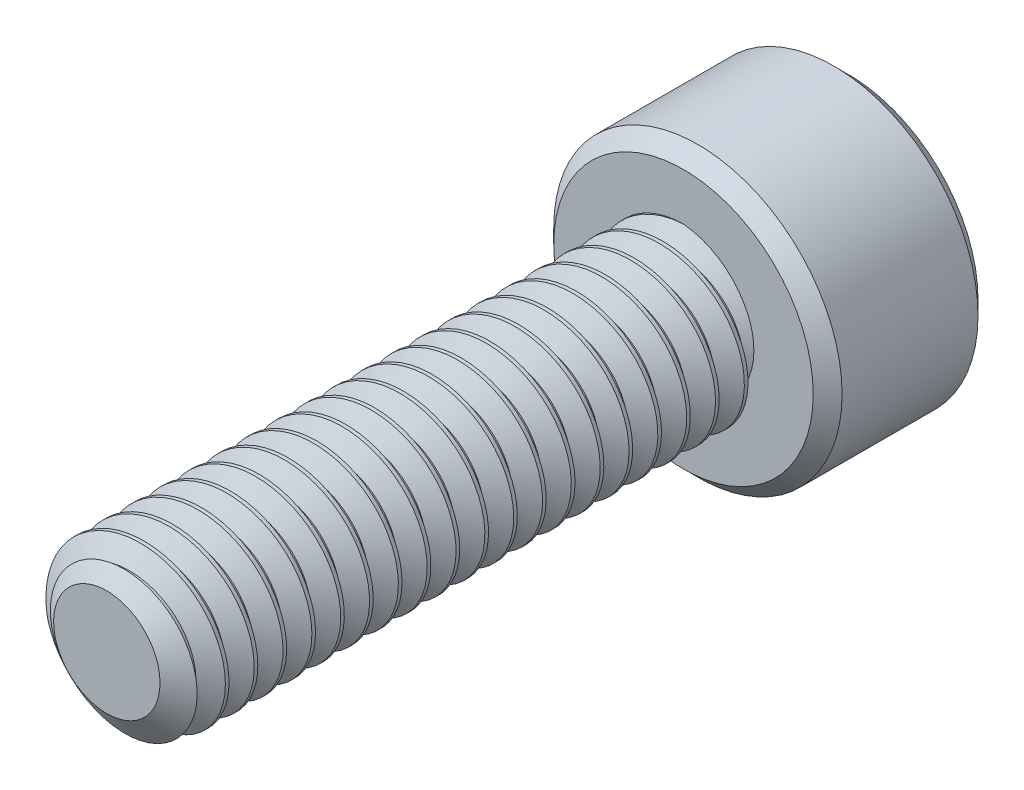
SolidWorks part; units mm, degrees
note: '?' marks a value the reader was unsure of.
other "DetailItem1"
material "Stainless Steel (ferritic)"
ref_plane "Front Plane" through (0, 0, 0) normal (0, 0, 1) x (1, 0, 0)
ref_plane "Top Plane" through (0, 0, 0) normal (0, 1, 0) x (1, 0, 0)
ref_plane "Right Plane" through (0, 0, 0) normal (1, 0, 0) x (0, 0, -1)
sketch "Sketch1" plane through (0, 0, 0) normal (0, 0, 1) x (1, 0, 0)
  circle A0 centre (0, 0) radius 2
  dimension "OD" = 4
extrude "Extrude1" add sketch "Sketch1" against normal blind 14
sketch "Sketch2" plane through (0, 0, 0) normal (0, 0, 1) x (1, 0, 0)
  circle A0 centre (0, 0) radius 2 construction
  circle A1 centre (0, 0) radius 2
curve "Helix/Spiral1" pitch 0.7 height 14.7 radius 2 centre (0, 0, 0) axis (0, 0, -1) start towards (0, 1, 0) parameters "pitch"=0.7
sketch "Sketch3" plane through (0, 0, 0) normal (1, 0, 0) x (0, 0, -1)
  line L0 (-0.6125, 2) -> (-0.35, 1.5453)
  line L1 (-0.35, 1.5453) -> (-0.2625, 1.5453)
  line L2 (-0.2625, 1.5453) -> (0, 2)
  line L3 (-0.6125, 2) -> (0, 2)
  line L4 (-0.3062, 2) -> (-0.3062, 1.5453) construction
  line L5 (-0.4812, 1.7727) -> (-0.1312, 1.7727) construction
  line L6 (0, 2) -> (0, -2) construction
  dimension "D1" = 0.0875
  dimension "D2" = 0.35
  dimension "D3" = 60
sweep "Cut-Sweep1" cut profiles "Sketch3" path "Helix/Spiral1" align with end faces yes
sketch "Sketch4" plane through (0, 0, 0) normal (1, 0, 0) x (0, 0, -1)
  line L0 (0.4962, 2) -> (0, 1.2913)
  line L1 (0, 1.2913) -> (0, 2)
  line L2 (0.4962, 2) -> (0, 2)
  line L3 (-0.6125, 2) -> (0, 2) construction
  line L4 (0, 0) -> (7.0209, 0) construction
  dimension "D1" = 55
  dimension "D2" = 0.254
revolve "Cut-Revolve1" cut sketch "Sketch4" angle 360 about L4
sketch "Sketch6" plane through (0, 0, -14) normal (0, 0, -1) x (-1, 0, 0)
  circle A0 centre (0, 0) radius 3.5
  dimension "head dia" = 7
extrude "Extrude2" add sketch "Sketch6" along normal blind 4
sketch "Sketch7" plane through (0, 0, -18) normal (0, 0, -1) x (-1, 0, 0)
  line L1 (0, 1.7321) -> (-1.5, 0.866)
  line L2 (-1.5, 0.866) -> (-1.5, -0.866)
  line L3 (-1.5, -0.866) -> (0, -1.7321)
  line L4 (0, -1.7321) -> (1.5, -0.866)
  line L5 (1.5, -0.866) -> (1.5, 0.866)
  line L6 (1.5, 0.866) -> (0, 1.7321)
  circle A0 centre (0, 0) radius 1.5 construction
  dimension "hex dia" = 3
extrude "Cut-Extrude1" cut sketch "Sketch7" against normal blind 2.25
sketch "Sketch8" plane through (0, 0, -18) normal (0, 0, -1) x (-1, 0, 0)
  circle A0 centre (0, 0) radius 1.7321
extrude "Cut-Extrude2" cut sketch "Sketch8" against normal through all draft 45
chamfer "Chamfer1" distance 0.35 angle 45 2 edges at (-3.5, 0, -18) (-3.5, 0, -14)
sketch "Sketch10" plane through (0, 0, -14) normal (0, 0, 1) x (1, 0, 0)
  circle A1 centre (0, 0) radius 2
  circle A2 centre (0, 0) radius 2
  dimension "D1" = 0
ref_plane "Plane1" through (0, 0, 0) normal (0, 0, 1) x (1, 0, 0)
extrude "partial thread" [suppressed] add sketch "Sketch10" along normal up to surface (10 mm away) separate body
chamfer "Chamfer2" [suppressed] distance 0.08 angle 45
combine bodies "Combine1" [suppressed] operation type? add bodies to combine 107 108
sketch "Sketch9" plane through (0, 0, 0) normal (1, 0, 0) x (0, 0, -1)
  line L0 (0, 2) -> (0, -2) construction
  line L1 (1.75, 2) -> (1.75, -2) construction
  dimension "D1" = 1.75
equation "\"D3@Helix/Spiral1\" = \"screw length@Extrude1\"+\"pitch@Helix/Spiral1\""
equation "\"D1@Sketch3\" = \"pitch@Helix/Spiral1\"*.125"
equation "\"D2@Sketch3\" = \"pitch@Helix/Spiral1\"*.5"
equation "\"D1@Cut-Extrude1\" = \"hex dia@Sketch7\"*.75"
equation "\"D1@Chamfer1\" = \"head dia@Sketch6\"*.05"
equation "\"D1@Sketch9\" = \"pitch@Helix/Spiral1\"*2.5"
equation "\"D1@Chamfer2\"=\"OD@Sketch1\"*.02"
